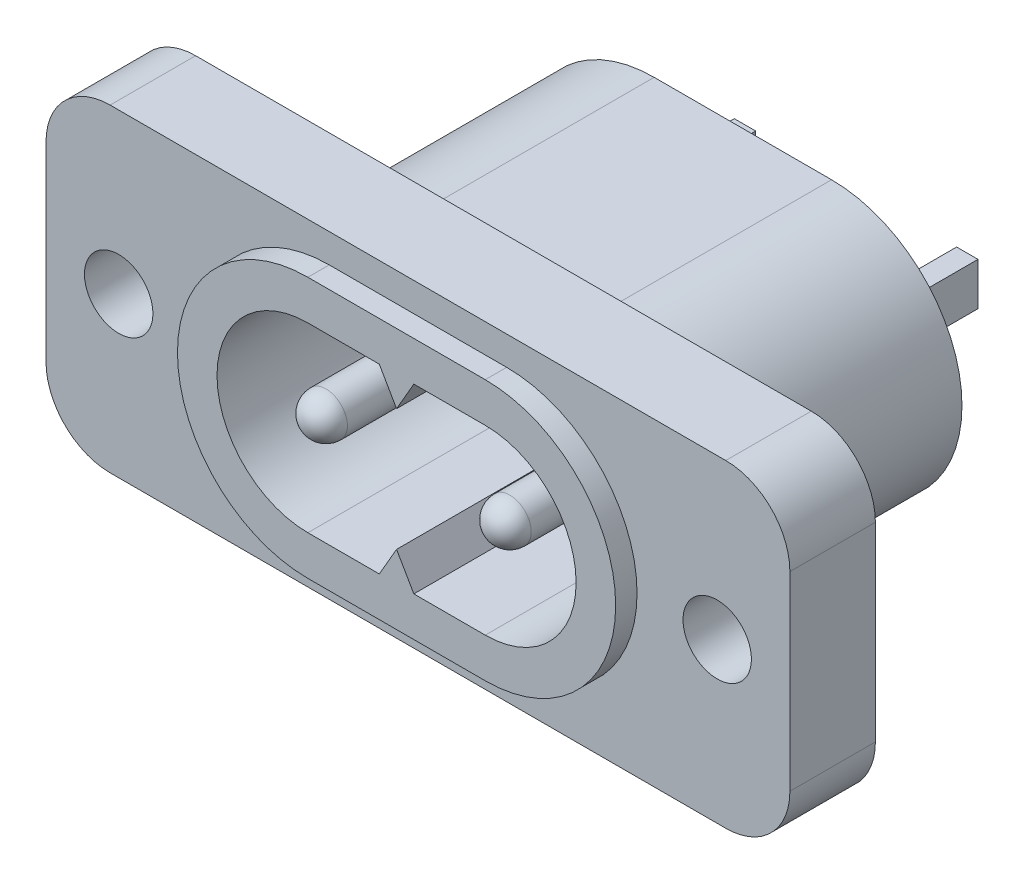
SolidWorks part; units mm, degrees
ref_plane "Front Plane" through (0, 0, 0) normal (0, 0, 1) x (1, 0, 0)
ref_plane "Top Plane" through (0, 0, 0) normal (0, 1, 0) x (1, 0, 0)
ref_plane "Right Plane" through (0, 0, 0) normal (1, 0, 0) x (0, 0, -1)
sketch "Sketch1" plane through (0, 0, 0) normal (0, 0, 1) x (1, 0, 0)
  line L0 (0, 10.1366) -> (0, -10.1366) construction
  line L1 (-14.4, 7.45) -> (14.4, 7.45)
  line L2 (-17.4, 4.45) -> (-17.4, -4.45)
  line L3 (-14.4, -7.45) -> (14.4, -7.45)
  line L4 (17.4, 4.45) -> (17.4, -4.45)
  line L5 (-17.4, 7.45) -> (17.4, -7.45) construction
  line L6 (-17.4, -7.45) -> (17.4, 7.45) construction
  line L7 (-4.15, 4.25) -> (-0.8083, 4.25)
  line L8 (-0.8083, 4.25) -> (0, 2.85)
  line L9 (0, 0) -> (-17.8389, 0) construction
  line L10 (-4.15, -4.25) -> (-0.8083, -4.25)
  line L11 (-0.8083, -4.25) -> (0, -2.85)
  line L12 (0.8083, -4.25) -> (0, -2.85)
  line L13 (4.15, -4.25) -> (0.8083, -4.25)
  line L14 (4.15, 4.25) -> (0.8083, 4.25)
  line L15 (0.8083, 4.25) -> (0, 2.85)
  line L16 (-8.4, 0) -> (-8.4, -5.471) construction
  arc A0 (14.4, 7.45) -> (17.4, 4.45) centre (14.4, 4.45) cw
  arc A1 (17.4, -4.45) -> (14.4, -7.45) centre (14.4, -4.45) cw
  arc A2 (-17.4, -4.45) -> (-14.4, -7.45) centre (-14.4, -4.45) ccw
  arc A3 (-17.4, 4.45) -> (-14.4, 7.45) centre (-14.4, 4.45) cw
  circle A4 centre (14, 0) radius 1.6
  circle A5 centre (-14, 0) radius 1.6
  arc A6 (-4.15, 4.25) -> (-4.15, -4.25) centre (-4.15, 0) ccw
  arc A7 (4.15, 4.25) -> (4.15, -4.25) centre (4.15, 0) cw
  point P0 (0, 0)
  dimension "D2" = 3
  dimension "D4" = 3.2
  dimension "D6" = 60
  dimension "D1" = 14.9
  dimension "D3" = 34.8
  dimension "D5" = 14
  dimension "D7" = 8.4
  dimension "D8" = 8.5
  dimension "D9" = 1.4
extrude "Boss-Extrude1" add sketch "Sketch1" along normal mid plane 4
sketch "Sketch2" plane through (0, 0, 2) normal (0, 0, 1) x (1, 0, 0)
  line L0 (-4.15, 0) -> (4.15, 0) construction
  line L1 (-4.15, 6.1) -> (4.15, 6.1)
  line L2 (-4.15, -6.1) -> (4.15, -6.1)
  line L3 (10.25, 0) -> (10.25, 12.2074) construction
  line L4 (-10.25, 0) -> (-10.25, 12.8806) construction
  line L5 (-0.8083, 4.25) -> (-4.15, 4.25) construction
  line L6 (0.8083, 4.25) -> (0, 2.85) construction
  line L7 (0, 2.85) -> (-0.8083, 4.25) construction
  line L8 (4.15, 4.25) -> (0.8083, 4.25) construction
  line L9 (0.8083, -4.25) -> (4.15, -4.25) construction
  line L10 (0, -2.85) -> (0.8083, -4.25) construction
  line L11 (-0.8083, -4.25) -> (0, -2.85) construction
  line L12 (-4.15, -4.25) -> (-0.8083, -4.25) construction
  line L13 (0.8083, 4.25) -> (0, 2.85)
  line L14 (4.15, 4.25) -> (0.8083, 4.25)
  line L15 (0.8083, -4.25) -> (4.15, -4.25)
  line L16 (0, -2.85) -> (0.8083, -4.25)
  line L17 (-0.8083, -4.25) -> (0, -2.85)
  line L18 (-4.15, -4.25) -> (-0.8083, -4.25)
  line L19 (-0.8083, 4.25) -> (-4.15, 4.25)
  line L20 (0, 2.85) -> (-0.8083, 4.25)
  arc A0 (-4.15, 6.1) -> (-4.15, -6.1) centre (-4.15, 0) ccw
  arc A1 (4.15, -6.1) -> (4.15, 6.1) centre (4.15, 0) ccw
  arc A2 (-4.15, 4.25) -> (-4.15, -4.25) centre (-4.15, 0) ccw construction
  arc A3 (4.15, -4.25) -> (4.15, 4.25) centre (4.15, 0) ccw construction
  arc A4 (4.15, -4.25) -> (4.15, 4.25) centre (4.15, 0) ccw
  arc A5 (-4.15, 4.25) -> (-4.15, -4.25) centre (-4.15, 0) ccw
  point P3 (0, 0)
  dimension "D1" = 20.5
  dimension "D2" = 12.2
extrude "Boss-Extrude2" add sketch "Sketch2" along normal blind 1 and the other way blind 15.2
sketch "Sketch3" plane through (0, 0, 3) normal (0, 0, 1) x (1, 0, 0)
  line L0 (0.8083, 4.25) -> (0, 2.85) construction
  line L1 (4.15, 4.25) -> (0.8083, 4.25) construction
  line L2 (0.8083, -4.25) -> (4.15, -4.25) construction
  line L3 (0, -2.85) -> (0.8083, -4.25) construction
  line L4 (-0.8083, -4.25) -> (0, -2.85) construction
  line L5 (-4.15, -4.25) -> (-0.8083, -4.25) construction
  line L6 (-0.8083, 4.25) -> (-4.15, 4.25) construction
  line L7 (0, 2.85) -> (-0.8083, 4.25) construction
  line L8 (0.8083, 4.25) -> (0, 2.85)
  line L9 (4.15, 4.25) -> (0.8083, 4.25)
  line L10 (0.8083, -4.25) -> (4.15, -4.25)
  line L11 (0, -2.85) -> (0.8083, -4.25)
  line L12 (-0.8083, -4.25) -> (0, -2.85)
  line L13 (-4.15, -4.25) -> (-0.8083, -4.25)
  line L14 (-0.8083, 4.25) -> (-4.15, 4.25)
  line L15 (0, 2.85) -> (-0.8083, 4.25)
  arc A0 (4.15, -4.25) -> (4.15, 4.25) centre (4.15, 0) ccw construction
  arc A1 (-4.15, 4.25) -> (-4.15, -4.25) centre (-4.15, 0) ccw construction
  arc A2 (4.15, -4.25) -> (4.15, 4.25) centre (4.15, 0) ccw
  arc A3 (-4.15, 4.25) -> (-4.15, -4.25) centre (-4.15, 0) ccw
extrude "Boss-Extrude3" add sketch "Sketch3" along normal blind 1 from offset 9.8 offset against normal yes
sketch "Sketch4" plane through (0, 0, 0) normal (1, 0, 0) x (0, 0, -1)
  line L0 (0, 0) -> (13.8, 0) construction
  line L1 (13.2, 1) -> (15.8, 1)
  line L2 (13.2, -6.1) -> (13.2, 6.1) construction
  line L3 (15.8, 1) -> (15.8, -10.62) construction
  line L4 (13.8, -10.62) -> (13.8, -1) construction
  line L5 (13.8, -1) -> (13.2, -1)
  line L6 (13.2, -1) -> (13.2, 1)
  line L7 (-3, 6.1) -> (-3, -6.1) construction
  line L8 (-1.9966, -7.45) -> (4.5753, -7.45) construction
  line L9 (-2, -7.45) -> (2, -7.45) construction
  line L10 (14.8, -11.62) -> (11.4728, -11.62) construction
  line L11 (13.8, -1) -> (18.5, -1)
  line L12 (18.5, -1) -> (18.5, 1)
  line L13 (18.5, 1) -> (15.8, 1)
  line L14 (-3, 6.1) -> (-3, -6.1) construction
  arc A0 (15.8, -10.62) -> (13.8, -10.62) centre (14.8, -10.62) cw construction
  dimension "D1" = 18.8
  dimension "D2" = 2.6
  dimension "D3" = 4.17
  dimension "D4" = 2
  dimension "D5" = 2
  dimension "D6" = 21.5
extrude "Boss-Extrude4" add sketch "Sketch4" against normal mid plane 1 from offset 5.2 separate body
sketch "Sketch5" plane through (0, 0, -13.2) normal (0, 0, -1) x (-1, 0, 0)
  line L2 (4.15, 6.1) -> (-4.15, 6.1)
  line L3 (-4.15, -6.1) -> (4.15, -6.1)
  line L4 (4.15, 6.1) -> (-4.15, 6.1)
  line L5 (-4.15, -6.1) -> (4.15, -6.1)
  arc A2 (4.15, -6.1) -> (4.15, 6.1) centre (4.15, 0) ccw
  arc A3 (-4.15, 6.1) -> (-4.15, -6.1) centre (-4.15, 0) ccw
  arc A4 (4.15, -6.1) -> (4.15, 6.1) centre (4.15, 0) ccw
  arc A5 (-4.15, 6.1) -> (-4.15, -6.1) centre (-4.15, 0) ccw
  dimension "D1" = 0
extrude "Boss-Extrude6" add sketch "Sketch5" against normal blind 1
mirror "Mirror2" about plane through (0, 0, 0) normal (1, 0, 0) of "Boss-Extrude4"
sketch "Sketch6" plane through (0, 0, -5.8) normal (0, 0, 1) x (1, 0, 0)
  line L0 (0, 2.85) -> (0, -2.85) construction
  circle A0 centre (-4.3, 0) radius 1
  circle A1 centre (4.3, 0) radius 1
  dimension "D1" = 2
  dimension "D2" = 8.6
extrude "Boss-Extrude7" add sketch "Sketch6" along normal up to surface (8.8 mm away) up to face at (0, 0, 3)
fillet "Fillet1" radius 1 2 edges at (5.3, 0, 3) (-3.3, 0, 3)
